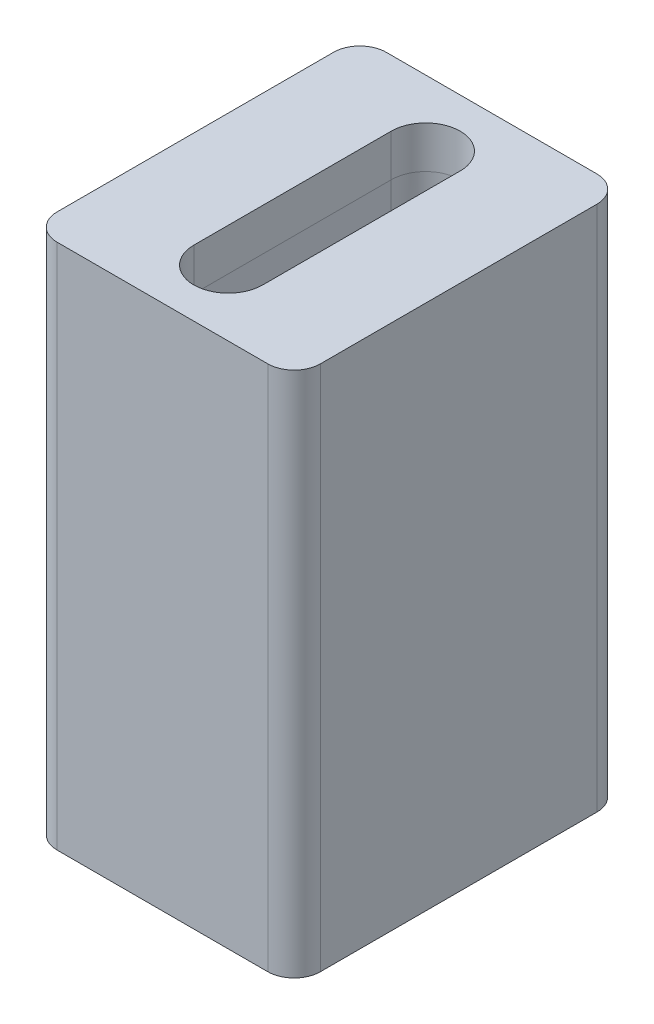
SolidWorks part; units mm, degrees
material "K110"
ref_plane "Front Plane" through (0, 0, 0) normal (0, 0, 1) x (1, 0, 0)
ref_plane "Top Plane" through (0, 0, 0) normal (0, 1, 0) x (1, 0, 0)
ref_plane "Right Plane" through (0, 0, 0) normal (1, 0, 0) x (0, 0, -1)
sketch "Sketch1" plane through (0, 0, 0) normal (0, 1, 0) x (1, 0, 0)
  line L3 (0, -7.5) -> (0, 7.5) construction
  line L4 (-2.62, -7.5) -> (-2.62, 7.5) construction
  line L5 (2.62, -7.5) -> (2.62, 7.5) construction
  line L6 (-8, -12.5) -> (8, -12.5)
  line L7 (-10, -10.5) -> (-10, 10.5)
  line L8 (-8, 12.5) -> (8, 12.5)
  line L9 (10, -10.5) -> (10, 10.5)
  line L10 (-10, -12.5) -> (10, 12.5) construction
  line L11 (-10, 12.5) -> (10, -12.5) construction
  arc A2 (-2.62, -7.5) -> (2.62, -7.5) centre (0, -7.5) ccw construction
  arc A3 (2.62, 7.5) -> (-2.62, 7.5) centre (0, 7.5) ccw construction
  arc A4 (-8, -12.5) -> (-10, -10.5) centre (-8, -10.5) cw
  arc A5 (8, -12.5) -> (10, -10.5) centre (8, -10.5) ccw
  arc A6 (8, 12.5) -> (10, 10.5) centre (8, 10.5) cw
  arc A7 (-10, 10.5) -> (-8, 12.5) centre (-8, 10.5) cw
  point P0 (0, 0)
  point P10 (0, 0)
  dimension "D1" = 15
  dimension "D3" = 2.62
  dimension "D5" = 2
  dimension "D2" = 25
  dimension "D4" = 20
extrude "Boss-Extrude1" add sketch "Sketch1" against normal blind 40
sketch "Sketch5" plane through (0, 0, 0) normal (0, 1, 0) x (1, 0, 0)
  line L0 (0, -7.5) -> (0, 7.5) construction
  line L1 (-2.62, -7.5) -> (-2.62, 7.5)
  line L2 (2.62, -7.5) -> (2.62, 7.5)
  arc A0 (-2.62, -7.5) -> (2.62, -7.5) centre (0, -7.5) ccw
  arc A1 (2.62, 7.5) -> (-2.62, 7.5) centre (0, 7.5) ccw
  point P4 (0, 0)
extrude "Cut-Extrude2" cut sketch "Sketch5" against normal up to next
sketch "Sketch7" plane through (0, 0, 0) normal (0, 0, 1) x (1, 0, 0)
  line L0 (2.62, -3.2) -> (3.2623, -40)
  line L1 (2.62, -40) -> (2.62, 0) construction
  line L2 (-8, -40) -> (8, -40) construction
  line L3 (3.2623, -40) -> (2.62, -40)
  line L4 (2.62, -40) -> (2.62, -3.2)
  line L5 (10, 0) -> (8, 0) construction
  dimension "D1" = 3.2
  dimension "D2" = 1
sketch "Sketch8" plane through (0, 0, 0) normal (0, 1, 0) x (1, 0, 0)
  line L0 (-2.62, 7.5) -> (-2.62, -7.5) construction
  line L1 (2.62, -7.5) -> (2.62, 7.5) construction
  line L2 (-2.62, 7.5) -> (-2.62, -7.5)
  line L3 (2.62, -7.5) -> (2.62, 7.5)
  arc A0 (2.62, 7.5) -> (-2.62, 7.5) centre (0, 7.5) ccw construction
  arc A1 (-2.62, -7.5) -> (2.62, -7.5) centre (0, -7.5) ccw construction
  arc A2 (2.62, 7.5) -> (-2.62, 7.5) centre (0, 7.5) ccw
  arc A3 (-2.62, -7.5) -> (2.62, -7.5) centre (0, -7.5) ccw
sweep "Cut-Sweep1" cut profiles "Sketch7" path "Sketch8"
hole_wizard "M3 Tapped Hole1" positions "Sketch11" profile "Sketch10" tap size "M3" standard "ISO"
sketch "Sketch11" plane through (0, -40, 0) normal (0, -1, 0) x (-1, 0, 0)
  line L0 (-8, 12.5) -> (8, 12.5) construction
  line L1 (-10, -10.5) -> (-10, 10.5) construction
  line L4 (10, 10.5) -> (10, -10.5) construction
  line L5 (8, -12.5) -> (-8, -12.5) construction
  point P0 (-7, 9.5)
  point P2 (7, -9.5)
  dimension "D1" = 3
  dimension "D2" = 3
  dimension "D3" = 3
  dimension "D4" = 3
sketch "Sketch10" plane through (7, -40, -9.5) normal (1, 0, 0) x (0, 0, -1)
  line L0 (0, 0) -> (0, 9.2511)
  line L1 (0, 9.2511) -> (1.25, 8.5)
  line L2 (1.25, 8.5) -> (1.25, 0.275)
  line L3 (1.25, 0.275) -> (1.525, 0)
  line L5 (1.525, 0) -> (0, 0)
  line L6 (-1.25, 0.275) -> (-1.525, 0) construction
  line L10 (0, 9.2511) -> (-1.25, 8.5) construction
  line L11 (0, -6.35) -> (0, 107.95) construction
  dimension "Tap Drill Dia." = 2.5
  dimension "Tap Drill Depth" = 8.5
  dimension "Near C'Sink Dia." = 3.05
  dimension "Near C'Sink Angle" = 90
  dimension "Drill Angle" = 118
cosmetic thread "Hole Thread1"
cosmetic thread "Hole Thread2"
